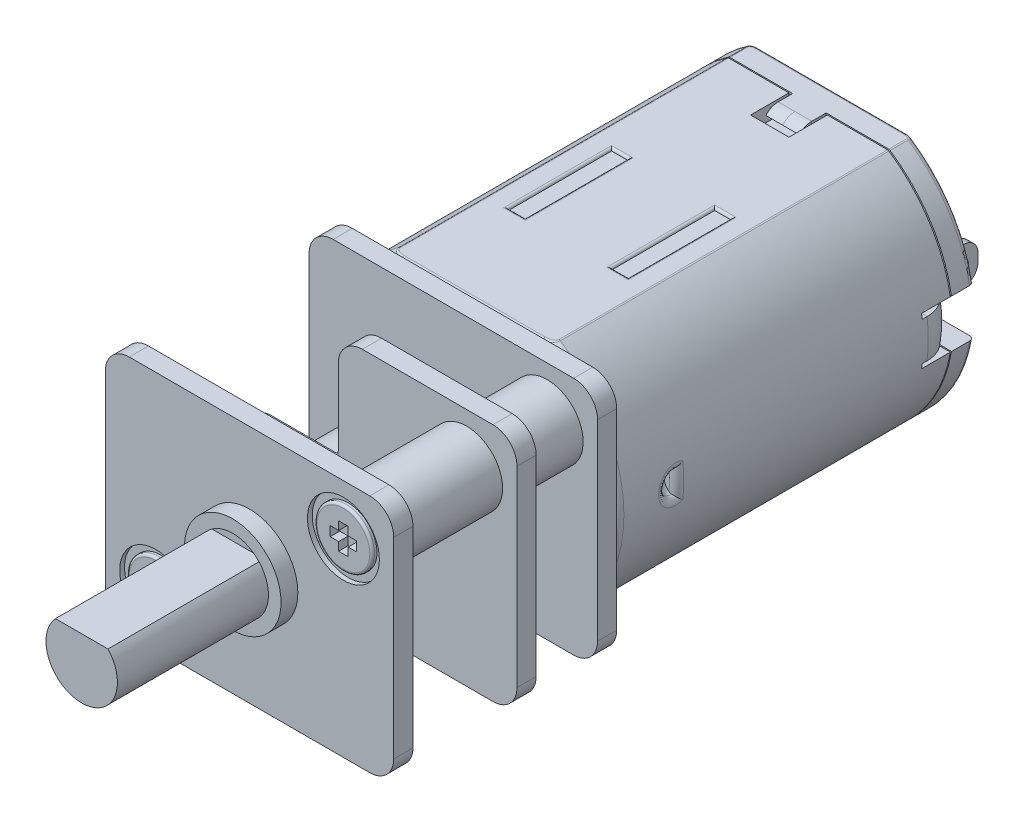
SolidWorks part; units mm, degrees
ref_plane "Alzado" through (0, 0, 0) normal (0, 0, 1) x (1, 0, 0)
ref_plane "Planta" through (0, 0, 0) normal (0, 1, 0) x (1, 0, 0)
ref_plane "Vista lateral" through (0, 0, 0) normal (1, 0, 0) x (0, 0, -1)
sketch "Croquis1" plane through (0, 0, 0) normal (0, 0, 1) x (1, 0, 0)
  line L0 (0, -5) -> (0, 5) construction
  line L1 (-3.3437, 5) -> (3.3437, 5)
  line L2 (-3.3437, -5) -> (3.3437, -5)
  arc A0 (-3.3437, 5) -> (-3.3437, -5) centre (0, 0) ccw
  arc A1 (3.3437, -5) -> (3.3437, 5) centre (0, 0) ccw
  point P6 (0, 0)
  point P9 (0, 5)
  point P12 (0, -5)
  dimension "D1" = 12.03
  dimension "D2" = 10
extrude "Saliente-Extruir2" add sketch "Croquis1" along normal mid plane 14
sketch "Croquis2" plane through (0, 0, -7) normal (0, 0, -1) x (-1, 0, 0)
  line L6 (-3.0913, -4.2) -> (3.0913, -4.2)
  line L7 (3.0913, 4.2) -> (-3.0913, 4.2)
  line L8 (-3.0913, -4.2) -> (3.0913, -4.2)
  line L9 (3.0913, 4.2) -> (-3.0913, 4.2)
  arc A6 (-3.0913, 4.2) -> (-3.0913, -4.2) centre (0, 0) ccw
  arc A7 (3.0913, -4.2) -> (3.0913, 4.2) centre (0, 0) ccw
  arc A8 (-3.0913, 4.2) -> (-3.0913, -4.2) centre (0, 0) ccw
  arc A9 (3.0913, -4.2) -> (3.0913, 4.2) centre (0, 0) ccw
  dimension "D1" = 0.8
extrude "Saliente-Extruir4" add sketch "Croquis2" along normal blind 0.05
sketch "Croquis3" plane through (0, 0, -7.05) normal (0, 0, -1) x (-1, 0, 0)
  line L2 (-3.3437, -5) -> (3.3437, -5)
  line L3 (3.3437, 5) -> (-3.3437, 5)
  line L4 (-3.3437, -5) -> (3.3437, -5)
  line L5 (3.3437, 5) -> (-3.3437, 5)
  arc A2 (-3.3437, 5) -> (-3.3437, -5) centre (0, 0) ccw
  arc A3 (3.3437, -5) -> (3.3437, 5) centre (0, 0) ccw
  arc A4 (-3.3437, 5) -> (-3.3437, -5) centre (0, 0) ccw
  arc A5 (3.3437, -5) -> (3.3437, 5) centre (0, 0) ccw
  dimension "D1" = 0
extrude "Saliente-Extruir5" add sketch "Croquis3" along normal blind 0.95
fillet "Redondeo1" radius 0.2 2 edges at (-6.015, 0, -8) (6.015, 0, -8)
sketch "Croquis4" plane through (0, 0, -8) normal (0, 0, -1) x (-1, 0, 0)
  circle A0 centre (0, 0) radius 2.515
  dimension "D1" = 5.03
extrude "Saliente-Extruir6" add sketch "Croquis4" along normal blind 1.15
sketch "Croquis5" plane through (0, 0, -9.15) normal (0, 0, -1) x (-1, 0, 0)
  circle A0 centre (0, 0) radius 1
  dimension "D1" = 2
extrude "Cortar-Extruir1" cut sketch "Croquis5" against normal blind 0.7
sketch "Croquis6" plane through (0, 5, 0) normal (0, 1, 0) x (1, 0, 0)
  line L0 (0, 7) -> (0, 5.4) construction
  line L1 (-3.0913, 7) -> (3.0913, 7) construction
  line L3 (-0.8, 7) -> (0.8, 7)
  line L4 (-0.8, 7) -> (-0.8, 5.4)
  line L5 (-0.8, 5.4) -> (0.8, 5.4)
  line L6 (0.8, 7) -> (0.8, 5.4)
  line L7 (-0.8, 7) -> (0.8, 5.4) construction
  line L8 (-0.8, 5.4) -> (0.8, 7) construction
  point P5 (0, 6.2)
  dimension "D1" = 1.6
  dimension "D2" = 1.6
extrude "Cortar-Extruir2" cut sketch "Croquis6" against normal blind 0.6
sketch "Croquis7" plane through (0, 0, -7.05) normal (0, 0, 1) x (1, 0, 0)
  line L0 (0, 5) -> (-0.7, 5)
  line L1 (-3.3437, 5) -> (3.3437, 5) construction
  line L2 (0, 5) -> (0.7, 5)
  line L3 (0.7, 5) -> (0.7, 4.6)
  line L4 (0.7, 4.6) -> (-0.7, 4.6)
  line L5 (-0.7, 4.6) -> (-0.7, 5)
  dimension "D1" = 0.7
  dimension "D2" = 0.7
  dimension "D3" = 0.4
sketch "Croquis8" plane through (0, 0, 0) normal (1, 0, 0) x (0, 0, -1)
  line L0 (7.05, 4.8) -> (6.45, 4.8)
  line L1 (7.05, 4.6) -> (7.05, 5) construction
  arc A0 (6.45, 4.8) -> (6.0898, 4.6341) centre (6.45, 4.326) ccw
  dimension "D2" = 0.474
  dimension "D1" = 0.6
sweep "Barrer1" add profiles "Croquis7" path "Croquis8"
sketch "Croquis9" plane through (0, 0, -8) normal (0, 0, -1) x (-1, 0, 0)
  line L0 (-6.015, 0) -> (-4.515, 0) construction
  line L1 (-4.515, 1) -> (-4.515, -1)
  line L2 (-4.515, 1) -> (-6.015, 1)
  line L3 (-6.015, 1) -> (-6.015, -1)
  line L4 (-6.015, -1) -> (-4.515, -1)
  arc A0 (-3.3437, 5) -> (-3.3437, -5) centre (0, 0) ccw construction
  point P10 (-4.515, 0)
  dimension "D1" = 2
  dimension "D2" = 1.5
extrude "Cortar-Extruir3" cut sketch "Croquis9" against normal blind 2.2
sketch "Croquis10" plane through (0, 0, -5.8) normal (0, 0, -1) x (-1, 0, 0)
  line L2 (-5.9616, 0.8) -> (-5.1616, 0.8)
  line L3 (-5.1616, 0.8) -> (-5.1616, -0.8)
  line L4 (-5.1616, -0.8) -> (-5.9616, -0.8)
  arc A0 (-5.9313, 1) -> (-5.9313, -1) centre (0, 0) ccw construction
  arc A1 (-5.9616, 0.8) -> (-5.9616, -0.8) centre (0, 0) ccw
  dimension "D3" = 0.8
sketch "Croquis11" plane through (0, 0, 0) normal (0, 1, 0) x (1, 0, 0)
  line L0 (5.5616, 5.8) -> (5.5616, 6)
  line L1 (5.1616, 5.8) -> (5.9616, 5.8) construction
  arc A0 (5.5616, 6) -> (4.7957, 6.8887) centre (4.663, 6) ccw
  dimension "D2" = 0.8985
  dimension "D1" = 0.2
sweep "Barrer2" add profiles "Croquis10" path "Croquis11"
mirror "Simetría2" about plane through (0, 0, 0) normal (1, 0, 0) of "Cortar-Extruir3", "Barrer2"
sketch "Croquis12" plane through (0, 5, 0) normal (0, 1, 0) x (1, 0, 0)
  line L0 (0, 8) -> (0, -3) construction
  line L1 (-2.9689, 8) -> (2.9689, 8) construction
  line L2 (-2.5, -3) -> (2.5, -3) construction
  line L3 (-2.5, -3) -> (-1.8, -3)
  line L4 (-1.8, -3) -> (-1.8, 1.3)
  line L5 (-1.8, 1.3) -> (-2.5, 1.3)
  line L6 (-2.5, 1.3) -> (-2.5, -3)
  line L7 (1.8, -3) -> (2.5, -3)
  line L8 (2.5, -3) -> (2.5, 1.3)
  line L9 (2.5, 1.3) -> (1.8, 1.3)
  line L10 (1.8, 1.3) -> (1.8, -3)
  point P8 (0, -3)
  dimension "D1" = 11
  dimension "D2" = 2.5
  dimension "D3" = 0.7
  dimension "D4" = 4.3
extrude "Cortar-Extruir4" cut sketch "Croquis12" against normal blind 0.1
fillet "Redondeo2" radius 0.1 8 edges at (2.15, 5, 3) (2.5, 5, 0.85) (1.8, 5, 0.85) (2.15, 5, -1.3) (-1.8, 5, 0.85) (-2.5, 5, 0.85) (-2.15, 5, 3) (-2.15, 5, -1.3)
sketch "Croquis13" plane through (0, -5, 0) normal (0, -1, 0) x (1, 0, 0)
  line L4 (2.5, 3) -> (1.8, 3)
  line L5 (2.5, -1.3) -> (2.5, 3)
  line L6 (1.8, -1.3) -> (2.5, -1.3)
  line L7 (1.8, 3) -> (1.8, -1.3)
  line L8 (2.5, 3) -> (1.8, 3)
  line L9 (2.5, -1.3) -> (2.5, 3)
  line L10 (1.8, -1.3) -> (2.5, -1.3)
  line L11 (1.8, 3) -> (1.8, -1.3)
  line L12 (-1.8, 3) -> (-2.5, 3)
  line L13 (-1.8, -1.3) -> (-1.8, 3)
  line L14 (-2.5, -1.3) -> (-1.8, -1.3)
  line L15 (-2.5, 3) -> (-2.5, -1.3)
  line L16 (-1.8, 3) -> (-2.5, 3)
  line L17 (-1.8, -1.3) -> (-1.8, 3)
  line L18 (-2.5, -1.3) -> (-1.8, -1.3)
  line L19 (-2.5, 3) -> (-2.5, -1.3)
  dimension "D1" = 0
  dimension "D2" = 0
extrude "Cortar-Extruir5" cut sketch "Croquis13" against normal blind 0.1
fillet "Redondeo3" radius 0.1 8 edges at (-2.15, -5, 3) (-2.5, -5, 0.85) (-2.15, -5, -1.3) (-1.8, -5, 0.85) (2.15, -5, 3) (1.8, -5, 0.85) (2.5, -5, 0.85) (2.15, -5, -1.3)
ref_plane "Plano1" through (0, 0, 7) normal (0, 0, 1) x (1, 0, 0)
ref_plane "Plano2" through (0, 0, 4.5) normal (0, 0, 1) x (1, 0, 0)
sketch "Croquis14" plane through (0, 0, 4.5) normal (0, 0, 1) x (1, 0, 0)
  line L0 (5.9943, 0.4983) -> (5.9943, -0.4983)
  line L1 (0, 0) -> (5.9943, 0) construction
  arc A0 (3.3437, -5) -> (3.3437, 5) centre (0, 0) ccw construction
  arc A1 (5.9943, 0.4983) -> (5.9943, -0.4983) centre (5.9943, 0) ccw
  point P6 (5.9943, 0)
revolve "Cortar-Revolución2" cut sketch "Croquis14" angle 180 about L0 reverse direction yes
fillet "Redondeo4" radius 0.3 2 edges at (6.015, 0, 4.5) (6.0147, -0.0562, 4.9947)
mirror "Simetría10" about plane through (0, 0, 0) normal (1, 0, 0) of "Cortar-Revolución2"
fillet "Redondeo5" radius 0.3 2 edges at (-6.0147, 0.0562, 4.9947) (-6.015, 0, 4.5)
fillet "Redondeo6" radius 0.3 2 edges at (-6.015, 0, 7) (6.015, 0, 7)
fillet "Redondeo7" radius 0.1 5 edges at (3.3437, 5, -0.15) (3.2741, 5, 6.8468) (-3.3437, 5, -0.15) (-3.2926, 5, 6.8271) (0, 5, 7)
fillet "Redondeo8" radius 0.1 5 edges at (-3.3437, -5, -0.15) (-3.2741, -5, 6.8468) (3.3437, -5, -0.15) (3.2926, -5, 6.8271) (0, -5, 7)
sketch "Croquis15" plane through (0, 0, 7) normal (0, 0, 1) x (1, 0, 0)
  line L1 (-6.015, -5) -> (6.015, -5)
  line L2 (-6.015, -5) -> (-6.015, 5)
  line L3 (-6.015, 5) -> (6.015, 5)
  line L4 (6.015, -5) -> (6.015, 5)
  line L5 (-6.015, -5) -> (6.015, 5) construction
  line L6 (-6.015, 5) -> (6.015, -5) construction
  point P0 (0, 0)
  dimension "D1" = 12.03
  dimension "D2" = 10
extrude "Saliente-Extruir8" add sketch "Croquis15" along normal blind 0.8
fillet "Redondeo9" radius 0.1 10 edges at (3.3437, -5, -7.425) (3.3012, -5, -7.8941) (-3.3437, -5, -7.425) (-3.3184, -5, -7.8735) (-3.3437, 5, -7.425) (-3.3012, 5, -7.8941) (3.3437, 5, -7.425) (3.3184, 5, -7.8735) (0, -5, -8) (0, 5, -8)
sketch "Croquis16" plane through (0, 0, 7.8) normal (0, 0, 1) x (1, 0, 0)
  line L0 (6.015, 5) -> (5.415, 5) construction
  line L1 (6.015, 5) -> (-6.015, 5) construction
  line L2 (5.415, 5) -> (5.415, 4.4) construction
  line L3 (5.415, 4.4) -> (5.415, 2.9) construction
  line L4 (5.415, 2.9) -> (3.915, 2.9) construction
  line L5 (-6.015, -5) -> (-5.415, -5) construction
  line L6 (-6.015, -5) -> (6.015, -5) construction
  line L7 (-5.415, -5) -> (-5.415, -4.4) construction
  line L8 (-5.415, -4.4) -> (-3.915, -4.4) construction
  line L9 (-3.915, -4.4) -> (-3.915, -2.9) construction
  circle A0 centre (3.915, 2.9) radius 1.5
  circle A1 centre (-3.915, -2.9) radius 1.5
  dimension "D5" = 0.6
  dimension "D1" = 0.6
  dimension "D2" = 0.6
  dimension "D3" = 1.5
  dimension "D4" = 1.5
  dimension "D6" = 0.6
  dimension "D7" = 1.5
  dimension "D8" = 1.5
extrude "Saliente-Extruir9" add sketch "Croquis16" along normal blind 8.5
sketch "Croquis17" plane through (0, 0, 16.3) normal (0, 0, 1) x (1, 0, 0)
  line L4 (6.015, -5) -> (6.015, 5)
  line L5 (6.015, 5) -> (-6.015, 5)
  line L6 (-6.015, 5) -> (-6.015, -5)
  line L7 (-6.015, -5) -> (6.015, -5)
  line L8 (6.015, -5) -> (6.015, 5)
  line L9 (6.015, 5) -> (-6.015, 5)
  line L10 (-6.015, 5) -> (-6.015, -5)
  line L11 (-6.015, -5) -> (6.015, -5)
  dimension "D1" = 0
extrude "Saliente-Extruir10" add sketch "Croquis17" against normal blind 0.8
ref_plane "Plano3" through (0, 0, 15.5) normal (0, 0, 1) x (1, 0, 0)
ref_plane "Plano4" through (0, 0, 11.16) normal (0, 0, 1) x (1, 0, 0)
sketch "Croquis18" plane through (0, 0, 11.16) normal (0, 0, 1) x (1, 0, 0)
  line L0 (-6.015, -0.09) -> (-1.435, -0.09)
  line L1 (-1.435, -0.09) -> (-1.435, 5)
  line L4 (6.015, -5) -> (6.015, 5)
  line L5 (6.015, 5) -> (-6.015, 5)
  line L6 (-6.015, 5) -> (-6.015, -5)
  line L7 (-6.015, -5) -> (6.015, -5)
  line L8 (6.015, -5) -> (6.015, 5)
  line L9 (6.015, 5) -> (-1.435, 5)
  line L10 (-6.015, -0.09) -> (-6.015, -5)
  line L11 (-6.015, -5) -> (6.015, -5)
  point P2 (-1.435, 5)
  point P5 (-6.015, -0.09)
  dimension "D2" = 7.45
  dimension "D3" = 4.91
  dimension "D1" = 0
extrude "Saliente-Extruir11" add sketch "Croquis18" against normal blind 0.8
fillet "Redondeo10" radius 1 14 edges at (-1.435, -0.09, 10.76) (-6.015, -5, 15.9) (-6.015, -0.09, 10.76) (-6.015, -5, 7.4) (-6.015, -5, 10.76) (6.015, -5, 15.9) (6.015, -5, 10.76) (-6.015, 5, 15.9) (6.015, 5, 15.9) (6.015, 5, 10.76) (-1.435, 5, 10.76) (-6.015, 5, 7.4) (6.015, -5, 7.4) (6.015, 5, 7.4)
sketch "Croquis19" plane through (0, 0, 16.3) normal (0, 0, 1) x (1, 0, 0)
  circle A0 centre (0, 0) radius 2.015
  dimension "D1" = 4.03
extrude "Saliente-Extruir12" add sketch "Croquis19" along normal blind 0.7
sketch "Croquis20" plane through (0, 0, 15.5) normal (0, 0, -1) x (-1, 0, 0)
  circle A1 centre (0, 0) radius 2.015
  circle A2 centre (0, 0) radius 2.015
  dimension "D1" = 0
extrude "Saliente-Extruir13" add sketch "Croquis20" along normal blind 2.62
sketch "Croquis21" plane through (0, 0, 17) normal (0, 0, 1) x (1, 0, 0)
  line L0 (0, -1.49) -> (0, 1.01) construction
  line L1 (-1.0954, 1.01) -> (1.0954, 1.01)
  arc A0 (-1.0954, 1.01) -> (1.0954, 1.01) centre (0, 0) ccw
  point P8 (0, 1.01)
  dimension "D1" = 2.98
  dimension "D2" = 2.5
extrude "Saliente-Extruir14" add sketch "Croquis21" along normal blind 9
sketch "Croquis22" plane through (0, 0, 16.3) normal (0, 0, 1) x (1, 0, 0)
  line L0 (6.015, 5) -> (6.015, 4.4) construction
  line L1 (6.015, 4.4) -> (5.415, 4.4) construction
  line L2 (5.415, 4.4) -> (5.415, 2.9) construction
  line L3 (5.415, 2.9) -> (3.915, 2.9) construction
  line L4 (-6.015, -5) -> (-6.015, -4.4) construction
  line L5 (-6.015, -4.4) -> (-5.415, -4.4) construction
  line L6 (-5.415, -4.4) -> (-5.415, -2.9) construction
  line L7 (-5.415, -2.9) -> (-3.915, -2.9) construction
  circle A0 centre (3.915, 2.9) radius 1.5
  circle A1 centre (-3.915, -2.9) radius 1.5
  dimension "D5" = 0.6
  dimension "D1" = 0.6
  dimension "D2" = 0.6
  dimension "D3" = 1.5
  dimension "D4" = 1.5
  dimension "D6" = 0.6
  dimension "D7" = 1.5
  dimension "D8" = 1.5
extrude "Cortar-Extruir6" cut sketch "Croquis22" against normal blind 0.2
sketch "Croquis23" plane through (0, 0, 16.1) normal (0, 0, 1) x (1, 0, 0)
  circle A0 centre (3.915, 2.9) radius 1.2
  circle A1 centre (-3.915, -2.9) radius 1.2
  dimension "D1" = 2.4
  dimension "D2" = 2.4
extrude "Saliente-Extruir15" add sketch "Croquis23" along normal up to surface (0.2 mm away) up to face at (-2.415, -2.9, 16.3)
sketch "Croquis24" plane through (0, 0, 16.3) normal (0, 0, 1) x (1, 0, 0)
  line L0 (-4.465, -3.1) -> (-4.115, -3.1)
  line L1 (-4.115, -2.35) -> (-4.115, -2.7)
  line L2 (4.465, 2.9) -> (3.365, 2.9) construction
  line L3 (3.915, 2.35) -> (3.915, 3.45) construction
  line L4 (3.365, 2.7) -> (3.715, 2.7)
  line L5 (3.715, 3.45) -> (3.715, 3.1)
  line L6 (3.365, 3.1) -> (3.715, 3.1)
  line L7 (4.115, 3.45) -> (4.115, 3.1)
  line L8 (3.715, 3.45) -> (4.115, 3.45)
  line L9 (4.465, 3.1) -> (4.465, 2.7)
  line L10 (4.115, 2.35) -> (3.715, 2.35)
  line L11 (3.365, 2.7) -> (3.365, 3.1)
  line L12 (4.115, 3.1) -> (4.465, 3.1)
  line L13 (3.715, 2.7) -> (3.715, 2.35)
  line L14 (-4.465, -2.7) -> (-4.115, -2.7)
  line L15 (4.115, 2.7) -> (4.465, 2.7)
  line L16 (-3.715, -2.35) -> (-3.715, -2.7)
  line L17 (4.115, 2.7) -> (4.115, 2.35)
  line L18 (-4.115, -2.35) -> (-3.715, -2.35)
  line L19 (-3.365, -2.7) -> (-3.365, -3.1)
  line L20 (-3.715, -3.45) -> (-4.115, -3.45)
  line L21 (-4.465, -3.1) -> (-4.465, -2.7)
  line L22 (-3.715, -2.7) -> (-3.365, -2.7)
  line L23 (-4.115, -3.1) -> (-4.115, -3.45)
  line L24 (-3.715, -3.1) -> (-3.365, -3.1)
  line L25 (-3.715, -3.1) -> (-3.715, -3.45)
  point P0 (3.915, 2.9)
  point P5 (3.915, 2.9)
  point P14 (3.915, 2.9)
  point P16 (-3.915, -2.9)
  point P23 (-3.915, -2.9)
  dimension "D1" = 1.1
extrude "Cortar-Extruir7" cut sketch "Croquis24" against normal blind 0.4
fillet "Redondeo11" radius 0.1 2 edges at (-2.715, -2.9, 16.3) (5.115, 2.9, 16.3)
sketch "Croquis25" plane through (0, 0, 17) normal (0, 0, 1) x (1, 0, 0)
  line L0 (1.0954, 1.01) -> (-1.0954, 1.01)
  arc A0 (1.0954, 1.01) -> (-1.0954, 1.01) centre (0, 0) ccw
extrude "Cortar-Extruir8" cut sketch "Croquis25" against normal blind 0.2
sketch "Croquis26" plane through (0, 0, -8) normal (0, 0, -1) x (-1, 0, 0)
  line L0 (2.515, 0) -> (-4.085, 0) construction
  line L1 (-4.085, 0.765) -> (-4.085, -0.765)
  line L2 (-4.085, 0.765) -> (-3.785, 0.765)
  line L3 (-3.785, 0.765) -> (-3.785, -0.765)
  line L4 (-3.785, -0.765) -> (-4.085, -0.765)
  line L5 (0, 0) -> (0, -0.4313) construction
  line L6 (3.785, -0.765) -> (4.085, -0.765)
  line L7 (3.785, 0.765) -> (3.785, -0.765)
  line L8 (4.085, 0.765) -> (4.085, -0.765)
  line L9 (4.085, 0.765) -> (3.785, 0.765)
  circle A0 centre (0, 0) radius 2.515 construction
  point P9 (-4.085, 0)
  dimension "D1" = 6.6
  dimension "D2" = 1.53
  dimension "D3" = 0.3
extrude "Saliente-Extruir16" add sketch "Croquis26" along normal blind 2
sketch "Croquis27" plane through (4.085, 0, 0) normal (1, 0, 0) x (0, 0, -1)
  line L8 (8.4, 0.365) -> (8.4, -0.365)
  line L9 (8.4, -0.365) -> (9.6, -0.365)
  line L10 (9.6, -0.365) -> (9.6, 0.365)
  line L11 (9.6, 0.365) -> (8.4, 0.365)
  line L12 (8.4, 0.365) -> (8.4, -0.365)
  line L13 (8.4, -0.365) -> (9.6, -0.365)
  line L14 (9.6, -0.365) -> (9.6, 0.365)
  line L15 (9.6, 0.365) -> (8.4, 0.365)
  dimension "D1" = 0.4
extrude "Cortar-Extruir9" cut sketch "Croquis27" against normal up to surface (0.3 mm away) up to face at (3.785, 0, -9)
fillet "Redondeo12" radius 0.6 2 edges at (3.935, -0.765, -10) (3.935, 0.765, -10)
fillet "Redondeo13" radius 0.4 4 edges at (3.935, 0.365, -8.4) (3.935, -0.365, -8.4) (3.935, -0.365, -9.6) (3.935, 0.365, -9.6)
sketch "Croquis28" plane through (-3.785, 0, 0) normal (1, 0, 0) x (0, 0, -1)
  line L0 (9.2, 0.365) -> (8.8, 0.365) construction
  line L1 (8.8, -0.365) -> (9.2, -0.365) construction
  line L2 (9.2, 0.365) -> (8.8, 0.365)
  line L3 (8.8, -0.365) -> (9.2, -0.365)
  arc A0 (8.8, 0.365) -> (8.4015, 0) centre (8.8, -0.035) ccw construction
  arc A1 (8.4015, 0) -> (8.8, -0.365) centre (8.8, 0.035) ccw construction
  arc A2 (9.2, -0.365) -> (9.5985, 0) centre (9.2, 0.035) ccw construction
  arc A3 (9.5985, 0) -> (9.2, 0.365) centre (9.2, -0.035) ccw construction
  arc A4 (8.8, 0.365) -> (8.4015, 0) centre (8.8, -0.035) ccw
  arc A5 (8.4015, 0) -> (8.8, -0.365) centre (8.8, 0.035) ccw
  arc A6 (9.2, -0.365) -> (9.5985, 0) centre (9.2, 0.035) ccw
  arc A7 (9.5985, 0) -> (9.2, 0.365) centre (9.2, -0.035) ccw
extrude "Cortar-Extruir10" cut sketch "Croquis28" against normal up to surface (0.3 mm away) up to face at (-4.085, 0, -9)
fillet "Redondeo14" radius 0.6 2 edges at (-3.935, -0.765, -10) (-3.935, 0.765, -10)
sketch "Sketch1" plane through (0, 0, 26) normal (0, 0, 1) x (1, 0, 0)
  line L0 (-1.0954, 1.01) -> (1.0954, 1.01)
  arc A0 (-1.0954, 1.01) -> (1.0954, 1.01) centre (0, 0) ccw
extrude "Cut-Extrude1" cut sketch "Sketch1" against normal blind 2.7
